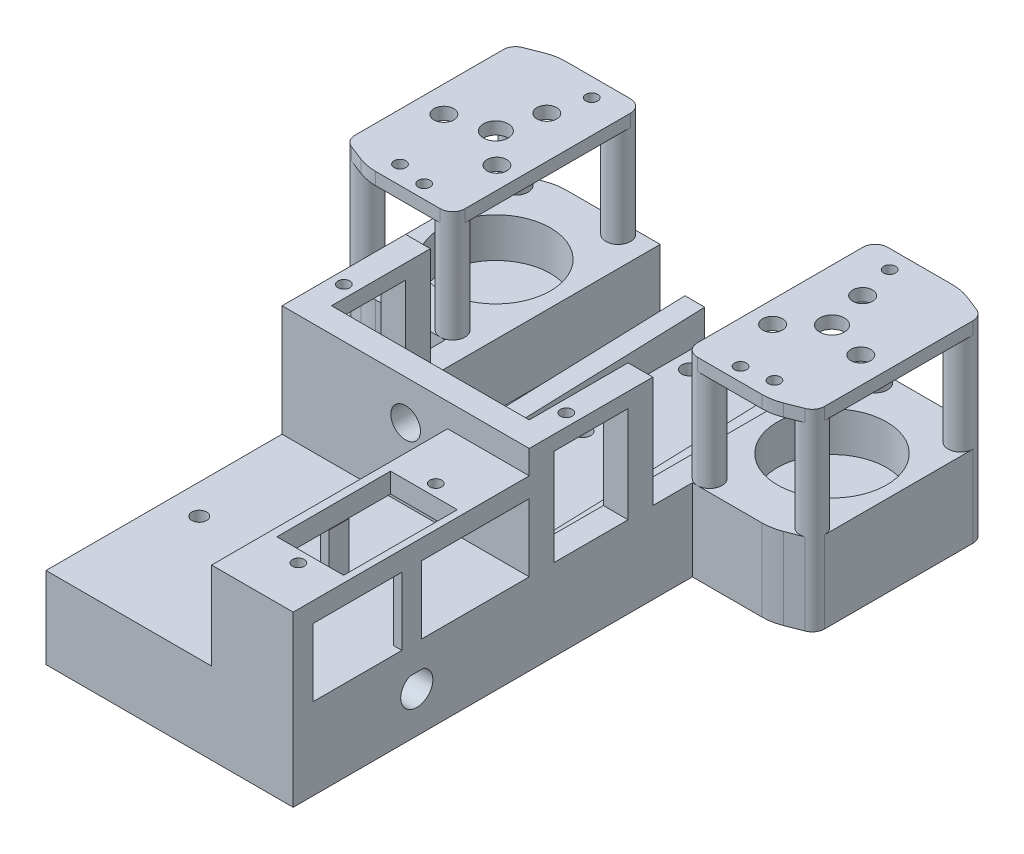
SolidWorks part; units mm, degrees
ref_plane "Front Plane" through (0, 0, 0) normal (0, 0, 1) x (1, 0, 0)
ref_plane "Top Plane" through (0, 0, 0) normal (0, 1, 0) x (1, 0, 0)
ref_plane "Right Plane" through (0, 0, 0) normal (1, 0, 0) x (0, 0, -1)
sketch "Sketch1" plane through (0, 0, 0) normal (0, 1, 0) x (1, 0, 0)
  line L0 (-54, 0) -> (54, 0) construction
  line L1 (-54, -20) -> (54, -20)
  line L2 (-54, -20) -> (-54, 20)
  line L3 (-54, 20) -> (54, 20)
  line L4 (54, -20) -> (54, 20)
  line L7 (0, 20) -> (0, -20) construction
  circle A0 centre (0, 0) radius 20 construction
  circle A2 centre (-34, 0) radius 8 construction
  circle A3 centre (-34, 0) radius 15 construction
  point P12 (-49, 0)
  point P15 (-19, 0)
  point P16 (-34, 15)
  point P17 (-34, 20)
  point P20 (0, 0)
  dimension "D1" = 40
  dimension "D2" = 16
  dimension "D3" = 30
  dimension "D4" = 38
  dimension "D5" = 5
  dimension "D6" = 40
extrude "Boss-Extrude1" add sketch "Sketch1" along normal blind 16.5
sketch "Sketch6" plane through (0, 0, 0) normal (0, 1, 0) x (1, 0, 0)
  circle A0 centre (0, 0) radius 20
  dimension "D1" = 40
sketch "Sketch2" plane through (0, 0, 0) normal (0, 1, 0) x (1, 0, 0)
  line L0 (0, -20) -> (0, 20) construction
  line L1 (54, 20) -> (-54, 20) construction
  line L2 (-45, 15) -> (-45, -15) construction
  line L3 (-26, 16.75) -> (-26, -16.75) construction
  circle A1 centre (-45, -15) radius 2.5
  circle A2 centre (-45, 15) radius 2.5
  circle A4 centre (0, 0) radius 20 construction
  circle A5 centre (-26, 16.75) radius 2.5
  circle A6 centre (-26, -16.75) radius 2.5
  circle A7 centre (26, -16.75) radius 2.5
  circle A8 centre (26, 16.75) radius 2.5
  circle A9 centre (45, 15) radius 2.5
  circle A10 centre (45, -15) radius 2.5
  point P3 (-45, 0)
  point P6 (0, 0)
  point P19 (-26, 0)
  dimension "D1" = 5
  dimension "D3" = 19
  dimension "D5" = 40
  dimension "D6" = 26
  dimension "D2" = 30
  dimension "D7" = 33.5
extrude "Boss-Extrude2" add sketch "Sketch2" along normal blind 20 from surface starting at face at (0, 16.5, 0)
sketch "Sketch3" plane through (0, 0, 0) normal (0, 1, 0) x (1, 0, 0)
  line L0 (-26, 19.25) -> (-41, 19.25)
  line L1 (0, 0) -> (-82.2021, 0) construction
  line L2 (-41, 19.25) -> (-45.9111, 17.3281)
  line L3 (-47.5, 15) -> (-47.5, -15)
  line L4 (-23.5, 16.75) -> (-23.5, 0)
  line L5 (-23.5, -16.75) -> (-23.5, 0)
  line L6 (-41, -19.25) -> (-45.9111, -17.3281)
  line L7 (-26, -19.25) -> (-41, -19.25)
  line L8 (0, 0) -> (0, 31.827) construction
  line L9 (26, -19.25) -> (41, -19.25)
  line L10 (41, -19.25) -> (45.9111, -17.3281)
  line L11 (23.5, -16.75) -> (23.5, 0)
  line L12 (23.5, 16.75) -> (23.5, 0)
  line L13 (47.5, 15) -> (47.5, -15)
  line L14 (41, 19.25) -> (45.9111, 17.3281)
  line L15 (26, 19.25) -> (41, 19.25)
  circle A0 centre (-45, 15) radius 2.5 construction
  circle A3 centre (-26, 16.75) radius 2.5 construction
  arc A4 (-45.9111, 17.3281) -> (-47.5, 15) centre (-45, 15) ccw
  arc A7 (-23.5, 16.75) -> (-26, 19.25) centre (-26, 16.75) ccw
  circle A8 centre (-45, 15) radius 2.5 construction
  arc A10 (-23.5, -16.75) -> (-26, -19.25) centre (-26, -16.75) cw
  arc A11 (-45.9111, -17.3281) -> (-47.5, -15) centre (-45, -15) cw
  arc A12 (45.9111, -17.3281) -> (47.5, -15) centre (45, -15) ccw
  arc A13 (23.5, -16.75) -> (26, -19.25) centre (26, -16.75) ccw
  arc A14 (23.5, 16.75) -> (26, 19.25) centre (26, 16.75) cw
  arc A15 (45.9111, 17.3281) -> (47.5, 15) centre (45, 15) cw
  point P11 (-47.5, 0)
  point P39 (47.5, 0)
  dimension "D1" = 15
extrude "Boss-Extrude3" add sketch "Sketch3" along normal blind 2.5 from surface starting at face at (-45, 36.5, 12.5)
sketch "Sketch5" plane through (0, 0, 0) normal (0, 1, 0) x (1, 0, 0)
  line L0 (0, 0) -> (-56.8582, 0) construction
  line L1 (-30.1292, 15.5247) -> (-37.8708, -15.5247) construction
  line L2 (0, 0) -> (0, 31.7941) construction
  circle A0 centre (-30.1292, 15.5247) radius 1.2
  circle A1 centre (-37.8708, -15.5247) radius 1.2
  circle A2 centre (-34, 0) radius 15 construction
  circle A3 centre (30.1292, 15.5247) radius 1.2
  circle A4 centre (37.8708, -15.5247) radius 1.2
  point P8 (-34, 0)
  dimension "D1" = 32
  dimension "D2" = 30
  dimension "D4" = 2.4
  dimension "D3" = 34
  dimension "D5" = 76
extrude "Cut-Extrude1" cut sketch "Sketch5" against normal up to surface and the other way through all from surface up to face at (-36.6317, 36.5, 0) starting at face at (-36.7505, 39, 0)
fillet "Fillet2" radius 10 4 edges at (-41, 37.75, -19.25) (-41, 37.75, 19.25) (41, 37.75, 19.25) (41, 37.75, -19.25)
sketch "Sketch7" plane through (0, 0, 0) normal (0, 1, 0) x (1, 0, 0)
  line L0 (-25, -20) -> (-25, -100)
  line L1 (-54, -20) -> (54, -20) construction
  line L2 (-25, -100) -> (25, -100)
  line L3 (0, 0) -> (0, -70.1383) construction
  line L4 (-25, -20) -> (25, -20)
  line L5 (25, -20) -> (25, -100)
  point P9 (0, -20)
  point P11 (0, -100)
  dimension "D1" = 50
  dimension "D2" = 80
extrude "Boss-Extrude4" add sketch "Sketch7" along normal up to surface (16.5 mm away) from surface up to face at (-45, 16.5, -17.5) starting at face at (0, 0, 0)
sketch "Sketch8" plane through (0, 0, 0) normal (0, 1, 0) x (1, 0, 0)
  line L0 (0, 0) -> (0, -21.5) construction
  circle A0 centre (-32, -16.5) radius 1.2
  circle A1 centre (32, -16.5) radius 1.2
  dimension "D1" = 2.4
  dimension "D2" = 64
  dimension "D3" = 16.5
extrude "Cut-Extrude2" cut sketch "Sketch8" against normal up to surface (2.5 mm away) from surface up to face at (-37.8708, 36.5, 14.3247) starting at face at (-37.8708, 39, 14.3247)
sketch "Sketch9" plane through (0, 0, 0) normal (0, 1, 0) x (1, 0, 0)
  line L0 (-26, 19.25) -> (-39.113, 19.25) construction
  line L1 (-42.7573, 18.5623) -> (-45.9111, 17.3281) construction
  line L2 (-47.5, 15) -> (-47.5, -15) construction
  line L3 (-45.9111, -17.3281) -> (-42.7573, -18.5623) construction
  line L4 (-39.113, -19.25) -> (-26, -19.25) construction
  line L5 (-23.5, -16.75) -> (-23.5, 16.75) construction
  line L6 (26, -19.25) -> (39.113, -19.25) construction
  line L7 (42.7573, -18.5623) -> (45.9111, -17.3281) construction
  line L8 (47.5, -15) -> (47.5, 15) construction
  line L9 (45.9111, 17.3281) -> (42.7573, 18.5623) construction
  line L10 (39.113, 19.25) -> (26, 19.25) construction
  line L11 (23.5, 16.75) -> (23.5, -16.75) construction
  line L12 (-26, 19.25) -> (-39.113, 19.25)
  line L13 (-42.7573, 18.5623) -> (-45.9111, 17.3281)
  line L14 (-47.5, 15) -> (-47.5, -15)
  line L15 (-45.9111, -17.3281) -> (-42.7573, -18.5623)
  line L16 (-39.113, -19.25) -> (-26, -19.25)
  line L17 (-23.5, -16.75) -> (-23.5, 16.75) construction
  line L18 (26, -19.25) -> (39.113, -19.25)
  line L19 (42.7573, -18.5623) -> (45.9111, -17.3281)
  line L20 (47.5, -15) -> (47.5, 15)
  line L21 (45.9111, 17.3281) -> (42.7573, 18.5623)
  line L22 (39.113, 19.25) -> (26, 19.25)
  line L23 (23.5, 16.75) -> (23.5, -16.75) construction
  line L24 (-26, 19.25) -> (26, 19.25)
  line L25 (26, -19.25) -> (25, -19.25)
  line L27 (-25, -19.25) -> (-25, -20)
  line L28 (-25, -20) -> (-54, -20)
  line L29 (25, -19.25) -> (25, -20)
  line L30 (25, -20) -> (54, -20)
  line L31 (-25, -19.25) -> (-26, -19.25)
  line L34 (54, -20) -> (54, 20)
  line L35 (54, 20) -> (-54, 20)
  line L36 (-54, 20) -> (-54, -20)
  line L37 (-54, -20) -> (-25, -20)
  line L38 (-25, -20) -> (-25, -100)
  line L39 (-25, -100) -> (25, -100)
  line L40 (25, -100) -> (25, -20)
  line L41 (25, -20) -> (54, -20)
  line L42 (54, -20) -> (54, 20)
  line L43 (54, 20) -> (-54, 20)
  line L44 (-54, 20) -> (-54, -20)
  line L45 (-54, -20) -> (-25, -20) construction
  line L46 (-25, -20) -> (-25, -100) construction
  line L47 (-25, -100) -> (25, -100) construction
  line L48 (25, -100) -> (25, -20) construction
  line L49 (25, -20) -> (54, -20) construction
  arc A0 (-39.113, 19.25) -> (-42.7573, 18.5623) centre (-39.113, 9.25) ccw construction
  arc A1 (-45.9111, 17.3281) -> (-47.5, 15) centre (-45, 15) ccw construction
  arc A2 (-47.5, -15) -> (-45.9111, -17.3281) centre (-45, -15) ccw construction
  arc A3 (-42.7573, -18.5623) -> (-39.113, -19.25) centre (-39.113, -9.25) ccw construction
  arc A4 (-26, -19.25) -> (-23.5, -16.75) centre (-26, -16.75) ccw construction
  arc A5 (-23.5, 16.75) -> (-26, 19.25) centre (-26, 16.75) ccw construction
  arc A6 (39.113, -19.25) -> (42.7573, -18.5623) centre (39.113, -9.25) ccw construction
  arc A7 (45.9111, -17.3281) -> (47.5, -15) centre (45, -15) ccw construction
  arc A8 (47.5, 15) -> (45.9111, 17.3281) centre (45, 15) ccw construction
  arc A9 (42.7573, 18.5623) -> (39.113, 19.25) centre (39.113, 9.25) ccw construction
  arc A10 (26, 19.25) -> (23.5, 16.75) centre (26, 16.75) ccw construction
  arc A11 (23.5, -16.75) -> (26, -19.25) centre (26, -16.75) ccw construction
  arc A12 (-39.113, 19.25) -> (-42.7573, 18.5623) centre (-39.113, 9.25) ccw
  arc A13 (-45.9111, 17.3281) -> (-47.5, 15) centre (-45, 15) ccw
  arc A14 (-47.5, -15) -> (-45.9111, -17.3281) centre (-45, -15) ccw
  arc A15 (-42.7573, -18.5623) -> (-39.113, -19.25) centre (-39.113, -9.25) ccw
  arc A16 (-26, -19.25) -> (-23.5, -16.75) centre (-26, -16.75) ccw construction
  arc A17 (-23.5, 16.75) -> (-26, 19.25) centre (-26, 16.75) ccw construction
  arc A18 (39.113, -19.25) -> (42.7573, -18.5623) centre (39.113, -9.25) ccw
  arc A19 (45.9111, -17.3281) -> (47.5, -15) centre (45, -15) ccw
  arc A20 (47.5, 15) -> (45.9111, 17.3281) centre (45, 15) ccw
  arc A21 (42.7573, 18.5623) -> (39.113, 19.25) centre (39.113, 9.25) ccw
  arc A22 (26, 19.25) -> (23.5, 16.75) centre (26, 16.75) ccw construction
  arc A23 (23.5, -16.75) -> (26, -19.25) centre (26, -16.75) ccw construction
  dimension "D1" = 0
extrude "Cut-Extrude3" cut sketch "Sketch9" along normal through all
sketch "Sketch10" plane through (0, 0, 0) normal (0, 0, 1) x (1, 0, 0)
  line L0 (25, 16.5) -> (-25, 16.5) construction
  line L1 (-20, 16.5) -> (20, 16.5)
  line L2 (-20, 16.5) -> (-20, 4)
  line L3 (-20, 4) -> (20, 4) construction
  line L4 (20, 16.5) -> (20, 4)
  line L5 (0, 0) -> (0, 59.3542) construction
  line L6 (-20, 4) -> (-15, 4)
  line L7 (-15, 4) -> (-15, 10)
  line L8 (-15, 10) -> (-11, 10)
  line L9 (-11, 10) -> (-11, 4)
  line L10 (-11, 4) -> (11, 4)
  line L11 (20, 4) -> (15, 4)
  line L12 (15, 4) -> (15, 10)
  line L13 (15, 10) -> (11, 10)
  line L14 (11, 10) -> (11, 4)
  point P6 (0, 4)
  point P20 (0, 4)
  dimension "D1" = 4
  dimension "D2" = 40
  dimension "D3" = 4
  dimension "D4" = 6
  dimension "D5" = 11
extrude "Cut-Extrude4" cut sketch "Sketch10" against normal through all from offset 47.25
sketch "Sketch11" plane through (0, 0, 0) normal (1, 0, 0) x (0, 0, -1)
  line L0 (-19.25, 16.5) -> (-100, 16.5) construction
  line L1 (-27.25, 16.5) -> (-52.25, 16.5)
  line L2 (-27.25, 16.5) -> (-27.25, 39)
  line L3 (-27.25, 39) -> (-52.25, 39)
  line L4 (-52.25, 16.5) -> (-52.25, 39)
  line L5 (-19.25, 16.5) -> (-19.25, 0) construction
  dimension "D1" = 8
  dimension "D2" = 25
extrude "Boss-Extrude5" add sketch "Sketch11" against normal up to surface (5 mm away) from surface up to face at (20, 10.25, 14) starting at face at (25, 8.25, 59.625)
extrude "Boss-Extrude6" add sketch "Sketch11<2>" along normal up to surface (5 mm away) from surface up to face at (-20, 10.25, 14) starting at face at (-25, 8.25, 59.625)
sketch "Sketch11<2>" plane through (0, 0, 0) normal (1, 0, 0) x (0, 0, -1) same geometry as "Sketch11"
sketch "Sketch12" plane through (0, 0, 0) normal (1, 0, 0) x (0, 0, -1)
  line L0 (-19.25, 16.5) -> (-27.25, 16.5) construction
  line L1 (-32.25, 16.5) -> (-47.25, 16.5)
  line L2 (-32.25, 16.5) -> (-32.25, 36)
  line L3 (-32.25, 36) -> (-47.25, 36)
  line L4 (-47.25, 16.5) -> (-47.25, 36)
  line L5 (-27.25, 16.5) -> (-27.25, 39) construction
  line L6 (-52.25, 39) -> (-52.25, 16.5) construction
  line L7 (-27.25, 39) -> (-52.25, 39) construction
  dimension "D1" = 5
  dimension "D2" = 5
  dimension "D3" = 3
extrude "Cut-Extrude5" cut sketch "Sketch12" against normal through all both and the other way through all
sketch "Sketch13" plane through (0, 0, 0) normal (0, 1, 0) x (1, 0, 0)
  line L0 (0, 0) -> (0, -74.0123) construction
  line L1 (-22.5, -52.25) -> (-22.5, -37.2081) construction
  line L2 (-20, -52.25) -> (-25, -52.25) construction
  circle A0 centre (-22.5, -42.25) radius 1.2
  circle A1 centre (22.5, -42.25) radius 1.2
  dimension "D1" = 2.4
  dimension "D2" = 10
extrude "Cut-Extrude6" cut sketch "Sketch13" against normal up to surface (3 mm away) from surface up to face at (22.5, 36, 39.75) starting at face at (-22.5, 39, 39.75)
sketch "Sketch14" plane through (0, 0, 0) normal (0, 0, 1) x (1, 0, 0)
  line L0 (20, 39) -> (25, 39) construction
  line L1 (-20, 16.5) -> (20, 16.5)
  line L2 (-20, 16.5) -> (-20, 39)
  line L3 (-20, 39) -> (20, 39)
  line L4 (20, 16.5) -> (20, 39)
  line L5 (20, 16.5) -> (20, 39) construction
extrude "Boss-Extrude7" add sketch "Sketch14" against normal up to surface (5 mm away) from surface up to face at (22.5, 26.25, 47.25) starting at face at (-22.5, 27.75, 52.25)
sketch "Sketch16" plane through (0, 0, 0) normal (0, 0, 1) x (1, 0, 0)
  line L0 (25, 16.5) -> (-25, 16.5) construction
  circle A0 centre (0, 31) radius 3
  point P9 (0, 16.5)
  dimension "D1" = 6
  dimension "D2" = 8
sketch "Sketch17" plane through (0, 0, 0) normal (1, 0, 0) x (0, 0, -1)
  line L0 (-100, 8.25) -> (-19.25, 8.25) construction
  line L1 (-100, 16.5) -> (-100, 0) construction
  line L2 (-19.25, 16.5) -> (-19.25, 0) construction
  line L3 (-76.4, 11.183) -> (-73.6, 11.183)
  arc A0 (-76.4, 11.183) -> (-73.6, 11.183) centre (-75, 8.25) ccw
  circle A1 centre (-90, 8.25) radius 1.6 construction
  circle A2 centre (-60, 8.25) radius 1.6 construction
  dimension "D1" = 6.5
  dimension "D3" = 15
  dimension "D4" = 15
  dimension "D6" = 3.2
  dimension "D2" = 2.8
  dimension "D5" = 25
extrude "Cut-Extrude8" cut sketch "Sketch17" against normal through all both and the other way through all
sketch "Sketch18" plane through (0, 0, 0) normal (1, 0, 0) x (0, 0, -1)
  line L0 (-14.6519, 10) -> (-14.6519, 11.5)
  line L1 (19.25, 10) -> (-47.25, 10) construction
  line L2 (-14.6519, 11.5) -> (-17.25, 10)
  line L3 (-17.25, 10) -> (-14.6519, 10)
  line L4 (-47.25, 4) -> (-47.25, 16.5) construction
  dimension "D1" = 30
  dimension "D2" = 1.5
  dimension "D3" = 30
extrude "Boss-Extrude8" [suppressed] add sketch "Sketch18" along normal up to surface (4 mm away) from surface up to face at (15, 7, 14) starting at face at (11, 7, 14)
sketch "Sketch19" plane through (0, 0, 0) normal (1, 0, 0) x (0, 0, -1)
  line L0 (19.25, 10) -> (-47.25, 7.6778)
  line L1 (-47.25, 4) -> (-47.25, 10) construction
  line L2 (-47.25, 7.6778) -> (-47.25, 10)
  line L3 (19.25, 10) -> (-47.25, 10) construction
  line L4 (-47.25, 10) -> (19.25, 10)
  dimension "D1" = 2
extrude "Cut-Extrude9" cut sketch "Sketch19" along normal up to surface (30 mm away) from surface up to face at (15, 7, 14) starting at face at (-15, 7, 14)
sketch "Sketch20" plane through (0, 0, 0) normal (1, 0, 0) x (0, 0, -1)
  line L0 (-100, 16.5) -> (-100, 34.2)
  line L1 (-100, 34.2) -> (-52.25, 34.2)
  line L2 (-52.25, 39) -> (-52.25, 16.5) construction
  line L3 (-92.15, 34.2) -> (-61.75, 34.2) construction
  line L4 (-100, 16.5) -> (-96, 16.5)
  line L5 (-52.25, 16.5) -> (-100, 16.5) construction
  line L6 (-96, 16.5) -> (-96, 30.2)
  line L7 (-96, 30.2) -> (-78, 30.2)
  line L8 (-52.25, 30.2) -> (-52.25, 34.2)
  line L9 (-78, 30.2) -> (-78, 16.5)
  line L10 (-78, 16.5) -> (-74, 16.5)
  line L11 (-74, 16.5) -> (-74, 30.2)
  line L12 (-74, 30.2) -> (-52.25, 30.2)
  dimension "D1" = 4
  dimension "D2" = 4
  dimension "D3" = 4
  dimension "D4" = 18
extrude "Boss-Extrude9" add sketch "Sketch20" against normal blind 16.5 from surface starting at face at (25, 8.0915, 75)
sketch "Sketch21" plane through (0, 0, 0) normal (0, 1, 0) x (1, 0, 0)
  line L1 (10.15, -88.45) -> (23.65, -88.45)
  line L2 (10.15, -88.45) -> (10.15, -65.45)
  line L3 (10.15, -65.45) -> (23.65, -65.45)
  line L12 (23.65, -88.45) -> (23.65, -65.45)
  line L13 (10.15, -88.45) -> (23.65, -65.45) construction
  line L14 (10.15, -65.45) -> (23.65, -88.45) construction
  arc A0 (17.45, -91.8026) -> (16.35, -91.8026) centre (16.9, -90.85) ccw construction
  arc A1 (16.35, -62.0974) -> (17.45, -62.0974) centre (16.9, -63.05) ccw construction
  arc A2 (17.45, -91.8026) -> (16.35, -91.8026) centre (16.9, -90.85) ccw construction
  arc A3 (16.35, -62.0974) -> (17.45, -62.0974) centre (16.9, -63.05) ccw construction
  circle A4 centre (16.9, -63.05) radius 1.2
  circle A5 centre (16.9, -90.85) radius 1.2
  point P12 (16.9, -76.95)
  dimension "D2" = 2.4
  dimension "D3" = 13.5
  dimension "D4" = 23
extrude "Cut-Extrude11" cut sketch "Sketch21" against normal up to surface (4 mm away) from surface up to face at (16.75, 30.2, 87) starting at face at (16.75, 34.2, 76.125)
sketch "Sketch22" plane through (0, 0, 0) normal (0, 1, 0) x (1, 0, 0)
  line L0 (-25, -75) -> (25, -75) construction
  line L1 (-25, -100) -> (-25, -52.25) construction
  line L4 (25, -73.6) -> (-25, -73.6)
  line L5 (25, -76.4) -> (25, -73.6)
  line L6 (-25, -76.4) -> (25, -76.4)
  line L7 (-25, -73.6) -> (-25, -76.4)
  line L8 (25, -73.6) -> (-25, -73.6) construction
  line L9 (25, -76.4) -> (25, -73.6) construction
  line L10 (-25, -76.4) -> (25, -76.4) construction
  line L11 (-25, -73.6) -> (-25, -76.4) construction
  circle A0 centre (-19, -75) radius 1.5
  circle A1 centre (-7, -75) radius 1.5
  circle A2 centre (5, -75) radius 1.5
  dimension "D2" = 3
  dimension "D3" = 6
  dimension "D4" = 18
  dimension "D5" = 30
  dimension "D1" = 0
extrude "Cut-Extrude12" cut sketch "Sketch22" against normal up to surface (5.317 mm away) from surface up to face at (0, 11.183, 75) starting at face at (33.5679, 16.5, 3.0937)
sketch "Sketch23" plane through (0, 0, 0) normal (0, 1, 0) x (1, 0, 0)
  circle A0 centre (-34, 0) radius 11.05
  circle A1 centre (34, 0) radius 11.05
  dimension "D1" = 22.1
extrude "Cut-Extrude13" cut sketch "Sketch23" against normal blind 8 from surface starting at face at (33.5679, 16.5, 3.0937)
sketch "Sketch24" plane through (0, 0, 0) normal (0, 1, 0) x (1, 0, 0)
  circle A0 centre (-31.9437, 8.2475) radius 2
  circle A1 centre (-27.8856, -5.9046) radius 2
  circle A2 centre (-42.1707, -2.3429) radius 2
  circle A3 centre (31.9437, 8.2475) radius 2
  circle A4 centre (27.8856, -5.9046) radius 2
  circle A5 centre (42.1707, -2.3429) radius 2
  circle A6 centre (-34, 0) radius 2.5
  circle A7 centre (34, 0) radius 2.5
  dimension "D1" = 4
  dimension "D2" = 5
extrude "Cut-Extrude14" cut sketch "Sketch24" against normal up to surface (2.5 mm away) from surface up to face at (-32, 36.5, 15.3) starting at face at (-32, 39, 15.3)
extrude "Cut-Extrude15" cut sketch "Sketch16" along normal through all
sketch "Sketch25" plane through (0, 0, 0) normal (0, 0, 1) x (1, 0, 0)
  line L0 (16.75, 34.2) -> (16.75, 12.0299) construction
  line L1 (10.25, 16.5) -> (23.25, 16.5)
  line L2 (10.25, 16.5) -> (10.25, 30.2)
  line L3 (10.25, 30.2) -> (23.25, 30.2)
  line L4 (23.25, 16.5) -> (23.25, 30.2)
  line L5 (10.25, 16.5) -> (23.25, 30.2) construction
  line L6 (10.25, 30.2) -> (23.25, 16.5) construction
  line L7 (8.5, 34.2) -> (25, 34.2) construction
  line L8 (8.5, 16.5) -> (-25, 16.5) construction
  point P0 (16.75, 23.35)
  dimension "D1" = 13
  dimension "D2" = 4
extrude "Cut-Extrude16" cut sketch "Sketch25" against normal up to surface (4 mm away) from surface up to face at (16.8, 25.6333, 74) starting at face at (16.8, 25.6333, 78)
sketch "Sketch26" plane through (0, 0, 0) normal (1, 0, 0) x (0, 0, -1)
  line L1 (-19.25, 36.5) -> (19.25, 36.5)
  line L2 (-19.25, 36.5) -> (-19.25, 39)
  line L3 (-19.25, 39) -> (19.25, 39)
  line L4 (19.25, 36.5) -> (19.25, 39)
extrude "Cut-Extrude17" [suppressed] cut sketch "Sketch26" against normal through all both and the other way through all
sketch "Sketch27" plane through (0, 0, 0) normal (0, 1, 0) x (1, 0, 0)
  line L0 (0, 30.0619) -> (0, -28.8432) construction
  circle A0 centre (-45, 15) radius 1.45
  circle A1 centre (-26, 16.75) radius 1.45
  circle A2 centre (-45, -15) radius 1.45
  circle A3 centre (45, -15) radius 1.45
  circle A4 centre (45, 15) radius 1.45
  circle A5 centre (26, 16.75) radius 1.45
  circle A6 centre (-26, -16.75) radius 1.45
  circle A7 centre (26, -16.75) radius 1.45
  dimension "D1" = 2.9
extrude "Cut-Extrude18" [suppressed] cut sketch "Sketch27" against normal blind 3.5 from surface starting at face at (-27.8856, 36.5, 3.9046)
sketch "Sketch28" plane through (0, 0, 0) normal (0, 1, 0) x (1, 0, 0)
  line L0 (0, 0) -> (0, -100) construction
  line L1 (-25, -100) -> (25, -100) construction
  line L2 (0, 0) -> (0, 19.25) construction
  line L3 (-39.113, 19.25) -> (39.113, 19.25) construction
  line L5 (-7.62, 12.795) -> (7.62, 12.795) construction
  line L6 (-7.62, 12.795) -> (-7.62, -8.795) construction
  line L7 (-7.62, -8.795) -> (7.62, -8.795) construction
  line L8 (7.62, 12.795) -> (7.62, -8.795) construction
  line L9 (-7.62, 12.795) -> (7.62, -8.795) construction
  line L10 (-7.62, -8.795) -> (7.62, 12.795) construction
  circle A1 centre (7.62, -8.795) radius 1.6
  circle A2 centre (7.62, 12.795) radius 1.6
  circle A3 centre (-7.62, -8.795) radius 1.6
  circle A4 centre (-7.62, 12.795) radius 1.6
  point P10 (0, 2)
  dimension "D4" = 3.2
  dimension "D1" = 15.24
  dimension "D2" = 21.59
  dimension "D3" = 2
extrude "Cut-Extrude19" cut sketch "Sketch28" along normal through all
equation "\"MDIA\"=16"
equation "\"D2@Sketch1\"=\"MDIA\""
equation "\"WDIA\"=30"
equation "\"D3@Sketch1\"=\"WDIA\""
